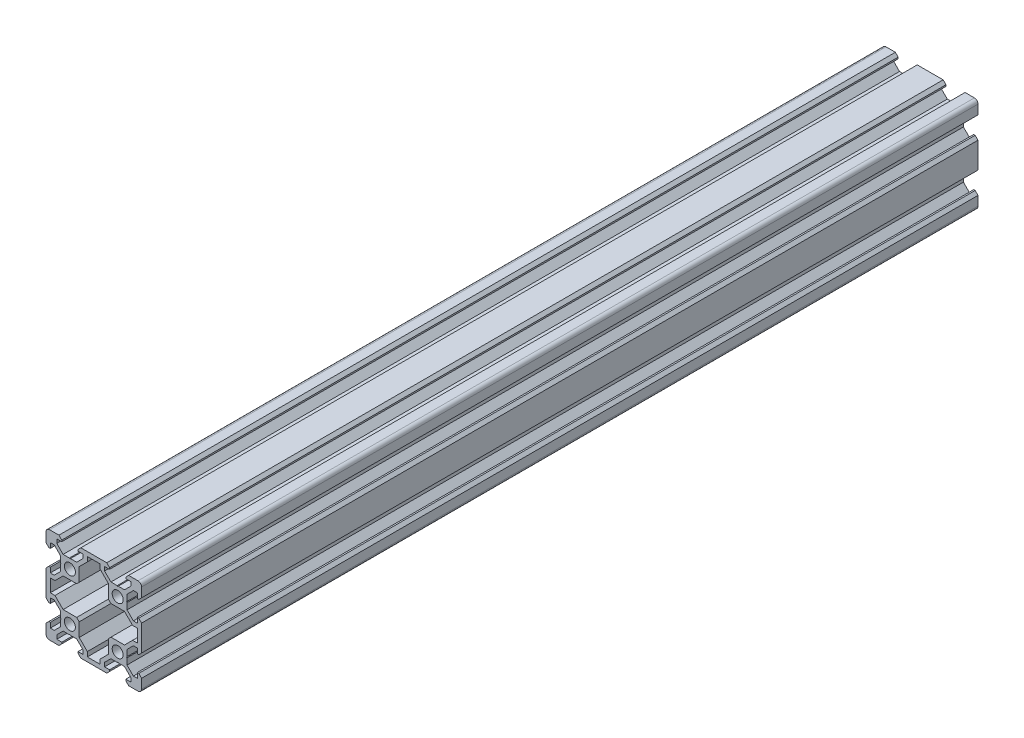
SolidWorks part; units mm, degrees
material "6061-T6 (SS)"
ref_plane "Front Plane" through (0, 0, 0) normal (0, 0, 1) x (1, 0, 0)
ref_plane "Top Plane" through (0, 0, 0) normal (0, 1, 0) x (1, 0, 0)
ref_plane "Right Plane" through (0, 0, 0) normal (1, 0, 0) x (0, 0, -1)
sketch "Sketch1" plane through (0, 0, 0) normal (0, 0, 1) x (1, 0, 0)
  line L1 (18.5, -20) -> (-18.5, -20)
  line L2 (20, -18.5) -> (20, 18.5)
  line L3 (18.5, 20) -> (-18.5, 20)
  line L4 (-20, -18.5) -> (-20, 18.5)
  line L5 (20, -20) -> (-20, 20) construction
  line L6 (20, 20) -> (-20, -20) construction
  circle A0 centre (-10, 10) radius 2.3
  circle A1 centre (10, -10) radius 2.3
  circle A2 centre (10, 10) radius 2.3
  circle A3 centre (-10, -10) radius 2.3
  arc A4 (-18.5, -20) -> (-20, -18.5) centre (-18.5, -18.5) cw
  arc A5 (18.5, -20) -> (20, -18.5) centre (18.5, -18.5) ccw
  arc A6 (20, 18.5) -> (18.5, 20) centre (18.5, 18.5) ccw
  arc A7 (-18.5, 20) -> (-20, 18.5) centre (-18.5, 18.5) ccw
  point P0 (0, 0)
  line B0 (-10, 10) -> (-10, 20) construction
  line B1 (-10, 13.69) -> (-10.21, 13.9)
  line B2 (-10.21, 13.9) -> (-12.8393, 13.9)
  line B3 (-12.8393, 13.9) -> (-15.5, 16.5607)
  line B4 (-15.5, 16.5607) -> (-15.5, 18.2)
  line B5 (-15.5, 18.2) -> (-13.395, 18.2)
  line B6 (-13.395, 18.2) -> (-13.395, 18.815)
  line B7 (-13.395, 18.815) -> (-14.58, 20)
  line B8 (-14.58, 20) -> (-5.42, 20)
  line B9 (-10, 10) -> (-15.9132, 15.9132) construction
  line B10 (-6.605, 18.815) -> (-5.42, 20)
  line B11 (-6.605, 18.2) -> (-6.605, 18.815)
  line B12 (-4.5, 18.2) -> (-6.605, 18.2)
  line B13 (-4.5, 16.5607) -> (-4.5, 18.2)
  line B14 (-7.1607, 13.9) -> (-4.5, 16.5607)
  line B15 (-9.79, 13.9) -> (-7.1607, 13.9)
  line B16 (-10, 13.69) -> (-9.79, 13.9)
  line B17 (10, 10) -> (10, 20) construction
  line B18 (10, 13.69) -> (9.79, 13.9)
  line B19 (9.79, 13.9) -> (7.1607, 13.9)
  line B20 (7.1607, 13.9) -> (4.5, 16.5607)
  line B21 (4.5, 16.5607) -> (4.5, 18.2)
  line B22 (4.5, 18.2) -> (6.605, 18.2)
  line B23 (6.605, 18.2) -> (6.605, 18.815)
  line B24 (6.605, 18.815) -> (5.42, 20)
  line B25 (5.42, 20) -> (14.58, 20)
  line B26 (10, 10) -> (4.0868, 15.9132) construction
  line B27 (13.395, 18.815) -> (14.58, 20)
  line B28 (13.395, 18.2) -> (13.395, 18.815)
  line B29 (15.5, 18.2) -> (13.395, 18.2)
  line B30 (15.5, 16.5607) -> (15.5, 18.2)
  line B31 (12.8393, 13.9) -> (15.5, 16.5607)
  line B32 (10.21, 13.9) -> (12.8393, 13.9)
  line B33 (10, 13.69) -> (10.21, 13.9)
  line B34 (-10, 10) -> (-20, 10) construction
  line B35 (-13.69, 10) -> (-13.9, 9.79)
  line B36 (-13.9, 9.79) -> (-13.9, 7.1607)
  line B37 (-13.9, 7.1607) -> (-16.5607, 4.5)
  line B38 (-16.5607, 4.5) -> (-18.2, 4.5)
  line B39 (-18.2, 4.5) -> (-18.2, 6.605)
  line B40 (-18.2, 6.605) -> (-18.815, 6.605)
  line B41 (-18.815, 6.605) -> (-20, 5.42)
  line B42 (-20, 5.42) -> (-20, 14.58)
  line B43 (-10, 10) -> (-15.9132, 4.0868) construction
  line B44 (-18.815, 13.395) -> (-20, 14.58)
  line B45 (-18.2, 13.395) -> (-18.815, 13.395)
  line B46 (-18.2, 15.5) -> (-18.2, 13.395)
  line B47 (-16.5607, 15.5) -> (-18.2, 15.5)
  line B48 (-13.9, 12.8393) -> (-16.5607, 15.5)
  line B49 (-13.9, 10.21) -> (-13.9, 12.8393)
  line B50 (-13.69, 10) -> (-13.9, 10.21)
  line B51 (-10, -10) -> (-20, -10) construction
  line B52 (-13.69, -10) -> (-13.9, -10.21)
  line B53 (-13.9, -10.21) -> (-13.9, -12.8393)
  line B54 (-13.9, -12.8393) -> (-16.5607, -15.5)
  line B55 (-16.5607, -15.5) -> (-18.2, -15.5)
  line B56 (-18.2, -15.5) -> (-18.2, -13.395)
  line B57 (-18.2, -13.395) -> (-18.815, -13.395)
  line B58 (-18.815, -13.395) -> (-20, -14.58)
  line B59 (-20, -14.58) -> (-20, -5.42)
  line B60 (-10, -10) -> (-15.9132, -15.9132) construction
  line B61 (-18.815, -6.605) -> (-20, -5.42)
  line B62 (-18.2, -6.605) -> (-18.815, -6.605)
  line B63 (-18.2, -4.5) -> (-18.2, -6.605)
  line B64 (-16.5607, -4.5) -> (-18.2, -4.5)
  line B65 (-13.9, -7.1607) -> (-16.5607, -4.5)
  line B66 (-13.9, -9.79) -> (-13.9, -7.1607)
  line B67 (-13.69, -10) -> (-13.9, -9.79)
  line B68 (-10, -10) -> (-10, -20) construction
  line B69 (-10, -13.69) -> (-9.79, -13.9)
  line B70 (-9.79, -13.9) -> (-7.1607, -13.9)
  line B71 (-7.1607, -13.9) -> (-4.5, -16.5607)
  line B72 (-4.5, -16.5607) -> (-4.5, -18.2)
  line B73 (-4.5, -18.2) -> (-6.605, -18.2)
  line B74 (-6.605, -18.2) -> (-6.605, -18.815)
  line B75 (-6.605, -18.815) -> (-5.42, -20)
  line B76 (-5.42, -20) -> (-14.58, -20)
  line B77 (-10, -10) -> (-4.0868, -15.9132) construction
  line B78 (-13.395, -18.815) -> (-14.58, -20)
  line B79 (-13.395, -18.2) -> (-13.395, -18.815)
  line B80 (-15.5, -18.2) -> (-13.395, -18.2)
  line B81 (-15.5, -16.5607) -> (-15.5, -18.2)
  line B82 (-12.8393, -13.9) -> (-15.5, -16.5607)
  line B83 (-10.21, -13.9) -> (-12.8393, -13.9)
  line B84 (-10, -13.69) -> (-10.21, -13.9)
  line B85 (10, -10) -> (10, -20) construction
  line B86 (10, -13.69) -> (10.21, -13.9)
  line B87 (10.21, -13.9) -> (12.8393, -13.9)
  line B88 (12.8393, -13.9) -> (15.5, -16.5607)
  line B89 (15.5, -16.5607) -> (15.5, -18.2)
  line B90 (15.5, -18.2) -> (13.395, -18.2)
  line B91 (13.395, -18.2) -> (13.395, -18.815)
  line B92 (13.395, -18.815) -> (14.58, -20)
  line B93 (14.58, -20) -> (5.42, -20)
  line B94 (10, -10) -> (15.9132, -15.9132) construction
  line B95 (6.605, -18.815) -> (5.42, -20)
  line B96 (6.605, -18.2) -> (6.605, -18.815)
  line B97 (4.5, -18.2) -> (6.605, -18.2)
  line B98 (4.5, -16.5607) -> (4.5, -18.2)
  line B99 (7.1607, -13.9) -> (4.5, -16.5607)
  line B100 (9.79, -13.9) -> (7.1607, -13.9)
  line B101 (10, -13.69) -> (9.79, -13.9)
  line B102 (10, 10) -> (20, 10) construction
  line B103 (13.69, 10) -> (13.9, 10.21)
  line B104 (13.9, 10.21) -> (13.9, 12.8393)
  line B105 (13.9, 12.8393) -> (16.5607, 15.5)
  line B106 (16.5607, 15.5) -> (18.2, 15.5)
  line B107 (18.2, 15.5) -> (18.2, 13.395)
  line B108 (18.2, 13.395) -> (18.815, 13.395)
  line B109 (18.815, 13.395) -> (20, 14.58)
  line B110 (20, 14.58) -> (20, 5.42)
  line B111 (10, 10) -> (15.9132, 15.9132) construction
  line B112 (18.815, 6.605) -> (20, 5.42)
  line B113 (18.2, 6.605) -> (18.815, 6.605)
  line B114 (18.2, 4.5) -> (18.2, 6.605)
  line B115 (16.5607, 4.5) -> (18.2, 4.5)
  line B116 (13.9, 7.1607) -> (16.5607, 4.5)
  line B117 (13.9, 9.79) -> (13.9, 7.1607)
  line B118 (13.69, 10) -> (13.9, 9.79)
  line B119 (10, -10) -> (20, -10) construction
  line B120 (13.69, -10) -> (13.9, -9.79)
  line B121 (13.9, -9.79) -> (13.9, -7.1607)
  line B122 (13.9, -7.1607) -> (16.5607, -4.5)
  line B123 (16.5607, -4.5) -> (18.2, -4.5)
  line B124 (18.2, -4.5) -> (18.2, -6.605)
  line B125 (18.2, -6.605) -> (18.815, -6.605)
  line B126 (18.815, -6.605) -> (20, -5.42)
  line B127 (20, -5.42) -> (20, -14.58)
  line B128 (10, -10) -> (15.9132, -4.0868) construction
  line B129 (18.815, -13.395) -> (20, -14.58)
  line B130 (18.2, -13.395) -> (18.815, -13.395)
  line B131 (18.2, -15.5) -> (18.2, -13.395)
  line B132 (16.5607, -15.5) -> (18.2, -15.5)
  line B133 (13.9, -12.8393) -> (16.5607, -15.5)
  line B134 (13.9, -10.21) -> (13.9, -12.8393)
  line B135 (13.69, -10) -> (13.9, -10.21)
  line B136 (-18.2, -2.7) -> (-18.2, 2.7)
  line B137 (-18.2, 2.7) -> (-16.2393, 2.7)
  line B138 (-16.2393, 2.7) -> (-12.8393, 6.1)
  line B139 (-12.8393, 6.1) -> (-7.1607, 6.1)
  line B140 (-10, 6.1) -> (-10, 0) construction
  line B141 (-10, 0) -> (-18.2, 0) construction
  line B142 (-12.8393, -6.1) -> (-7.1607, -6.1)
  line B143 (-16.2393, -2.7) -> (-12.8393, -6.1)
  line B144 (-18.2, -2.7) -> (-16.2393, -2.7)
  line B145 (-10, 6.1) -> (-10, 10) construction
  line B146 (-10, 10) -> (-15.0927, 4.9073) construction
  line B147 (-10, 10) -> (-6.3747, 6.3747) construction
  line B148 (2.7, 18.2) -> (2.7, 16.2393)
  line B149 (2.7, 16.2393) -> (6.1, 12.8393)
  line B150 (6.1, 12.8393) -> (6.1, 7.1607)
  line B151 (-6.1, 12.8393) -> (-6.1, 7.1607)
  line B152 (-2.7, 16.2393) -> (-6.1, 12.8393)
  line B153 (-2.7, 18.2) -> (-2.7, 16.2393)
  line B154 (2.7, 18.2) -> (-2.7, 18.2)
  line B155 (2.7, -18.2) -> (-2.7, -18.2)
  line B156 (-2.7, -18.2) -> (-2.7, -16.2393)
  line B157 (-2.7, -16.2393) -> (-6.1, -12.8393)
  line B158 (-6.1, -12.8393) -> (-6.1, -7.1607)
  line B159 (6.1, -12.8393) -> (6.1, -7.1607)
  line B160 (2.7, -16.2393) -> (6.1, -12.8393)
  line B161 (2.7, -18.2) -> (2.7, -16.2393)
  line B162 (0, 18.2) -> (0, -18.2) construction
  line B163 (12.8393, -6.1) -> (7.1607, -6.1)
  line B164 (16.2393, -2.7) -> (12.8393, -6.1)
  line B165 (18.2, -2.7) -> (16.2393, -2.7)
  line B166 (18.2, -2.7) -> (18.2, 2.7)
  line B167 (18.2, 2.7) -> (16.2393, 2.7)
  line B168 (16.2393, 2.7) -> (12.8393, 6.1)
  line B169 (12.8393, 6.1) -> (7.1607, 6.1)
  line B170 (-7.1607, 6.1) -> (-6.1, 7.1607)
  line B171 (6.1, 7.1607) -> (7.1607, 6.1)
  line B172 (7.1607, -6.1) -> (6.1, -7.1607)
  line B173 (-6.1, -7.1607) -> (-7.1607, -6.1)
  dimension "D4" = 4.6
  dimension "D5" = 1.5
  dimension "D1" = 40
  dimension "D2" = 10
  dimension "D3" = 10
sketch_block_instance "V Slot 2-1"
sketch_block "V Slot 2" parameters "D1"=10, "D2"=11, "D3"=4.3, "D4"=1.8, "D5"=0.21, "D6"=45, "D7"=9.16, "D8"=1.5, "D9"=6.79
sketch_block_instance "V Slot 2-2"
sketch_block_instance "V Slot 2-3"
sketch_block_instance "V Slot 2-4"
sketch_block_instance "V Slot 2-5"
sketch_block_instance "V Slot 2-6"
sketch_block_instance "V Slot 2-7"
sketch_block_instance "V Slot 2-8"
sketch_block_instance "Center Cutout 2-1"
sketch_block "Center Cutout 2" parameters "D1"=5.4, "D2"=12.2, "D3"=8.2, "D4"=45, "D5"=10, "D6"=1.5
extrude "Boss-Extrude1" add sketch "Sketch1" along normal blind 350 contours B135 B120 B121 B122 B123 B124 B125 B126 L2 B112 B113 B114 B115 B116 B117 B118 B103 B104 B105 B106 B107 B108 B109 A6 L3 B27 B28 B29 B30 B31 B32 B33 B18 B19 B20 B21 B22 B23 B24 B10 B11 B12 B13 B14 B15 B16 B1 B2 B3 region at (16.54, -19.4343, 0)
